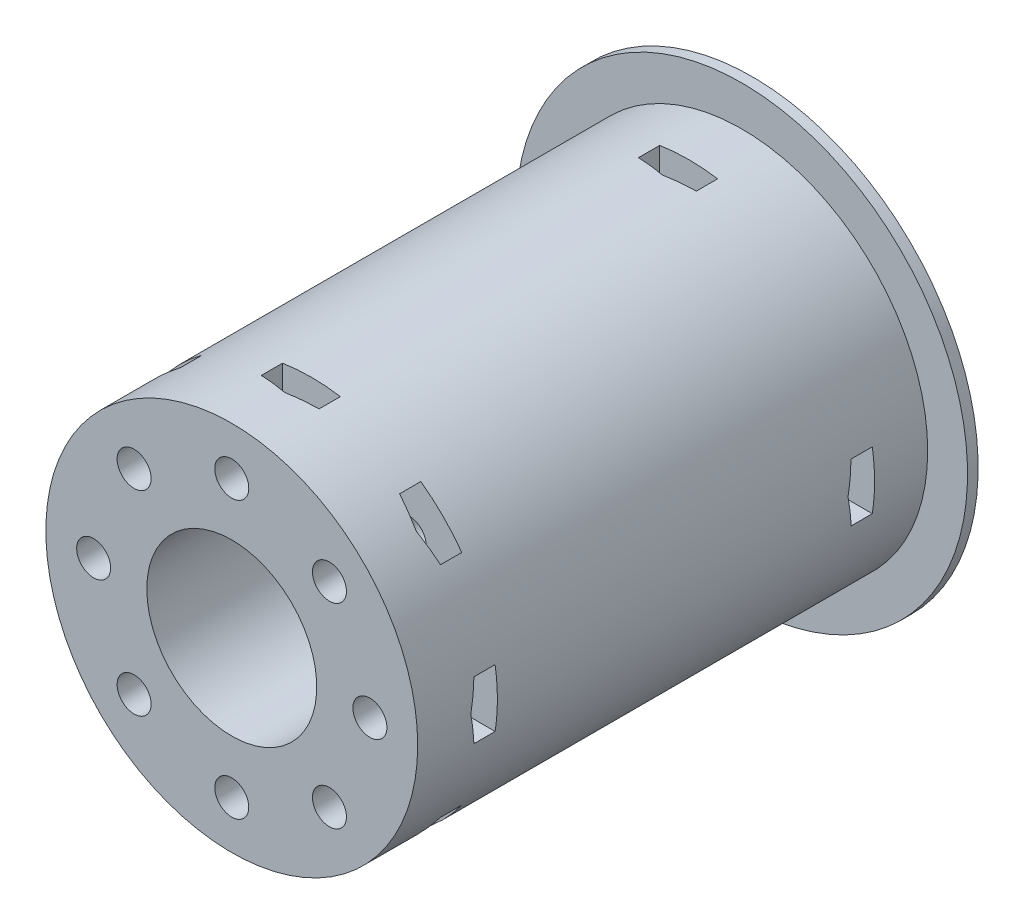
SolidWorks part; units mm, degrees
ref_plane "Front Plane" through (0, 0, 0) normal (1, 0, 0) x (0, 1, 0)
ref_plane "Top Plane" through (0, 0, 0) normal (0, 0, 1) x (0, 1, 0)
ref_plane "Right Plane" through (0, 0, 0) normal (0, 1, 0) x (-1, 0, 0)
sketch "Sketch1" plane through (0, 0, 0) normal (0, 0, 1) x (0, 1, 0)
  circle A0 centre (0, 0) radius 17.5
  dimension "D1" = 35
extrude "Boss-Extrude1" add sketch "Sketch1" along normal blind 24 and the other way blind 24
sketch "Sketch3" plane through (0, 0, -24) normal (0, 0, -1) x (1, 0, 0)
  circle A0 centre (0, 0) radius 21.25
  dimension "D1" = 42.5
extrude "Boss-Extrude2" add sketch "Sketch3" along normal blind 1
sketch "Sketch2" plane through (0, 0, 24) normal (0, 0, 1) x (1, 0, 0)
  line L0 (-2.725, 15.725) -> (-2.725, 17.2865)
  line L2 (-2.725, 15.725) -> (-2.725, 10.275)
  line L3 (-2.725, 10.275) -> (2.725, 10.275)
  line L4 (2.725, 15.725) -> (2.725, 10.275)
  line L5 (-2.725, 15.725) -> (2.725, 10.275) construction
  line L6 (-2.725, 10.275) -> (2.725, 15.725) construction
  line L7 (2.725, 15.725) -> (2.725, 17.2865)
  circle A0 centre (0, 0) radius 13 construction
  circle A1 centre (0, 13) radius 1.6
  circle A2 centre (0, 0) radius 17.5 construction
  arc A3 (-2.725, 17.2865) -> (2.725, 17.2865) centre (0, 0) cw
  dimension "D1" = 26
  dimension "D4" = 3.2
  dimension "D2" = 5.45
  dimension "D3" = 5.45
extrude "Cut-Extrude1" cut sketch "Sketch2" against normal through all contours A1
extrude "Cut-Extrude2" cut sketch "Sketch2<4>" against normal blind 2.5 from offset 5 offset against normal yes
sketch "Sketch2<4>" plane through (0, 0, 24) normal (0, 0, 1) x (1, 0, 0) same geometry as "Sketch2"
extrude "Cut-Extrude3" cut sketch "Sketch2<5>" along normal blind 2.5 from offset 43 offset against normal yes
sketch "Sketch2<5>" plane through (0, 0, 24) normal (0, 0, 1) x (1, 0, 0) same geometry as "Sketch2"
chamfer "Chamfer1" distance 2.725 distance2 0.5 2 edges at (-2.725, 13.7808, 19) (2.725, 13.7808, 19) first distance on face at (1.6, 13, 19)
chamfer "Chamfer2" distance 2.725 distance2 0.5 2 edges at (-2.725, 13.7808, -16.5) (2.725, 13.7808, -16.5) first distance on face at (0, 13.8341, -16.5)
pattern_circular "CirPattern1" count 8 over 360 about axis through (0, 0, -24) along (0, 0, 1) of "Cut-Extrude2", "Cut-Extrude1", "Chamfer1" reverse direction yes
pattern_circular "CirPattern3" count 4 over 360 about axis through (0, 0, -24) along (0, 0, 1) of "Cut-Extrude3", "Chamfer2"
sketch "Sketch4" plane through (0, 0, -25) normal (0, 0, -1) x (1, 0, 0)
  circle A0 centre (0, 0) radius 8
  dimension "D1" = 16
extrude "Cut-Extrude4" cut sketch "Sketch4" against normal through all both and the other way through all
sketch "Sketch5" plane through (0, 0, -25) normal (0, 0, -1) x (1, 0, 0)
  line L0 (-0.5, -10) -> (-0.5, -0.5)
  line L1 (-10, 0.5) -> (-0.5, 0.5)
  line L2 (-10, 0.5) -> (-10, -0.5)
  line L3 (-10, -0.5) -> (-0.5, -0.5)
  line L4 (10, 0.5) -> (10, -0.5)
  line L5 (-10, 0.5) -> (10, -0.5) construction
  line L6 (-10, -0.5) -> (10, 0.5) construction
  line L7 (-0.5, -10) -> (0.5, -10)
  line L8 (0.5, -10) -> (0.5, -0.5)
  line L9 (-0.5, 10) -> (0.5, 10)
  line L10 (-0.5, -10) -> (0.5, 10) construction
  line L11 (0.5, -10) -> (-0.5, 10) construction
  line L14 (-0.5, 0.5) -> (-0.5, 10)
  line L15 (0.5, 0.5) -> (0.5, 10)
  line L16 (0.5, 0.5) -> (10, 0.5)
  line L19 (0.5, -0.5) -> (10, -0.5)
  point P0 (0, 0)
  point P6 (0, 0)
  point P11 (0, 0)
  point P12 (23.112, -19.3365)
  dimension "D1" = 1
  dimension "D2" = 20
  dimension "D3" = 1
  dimension "D4" = 20
extrude "Cut-Extrude5" cut sketch "Sketch5" against normal blind 0.2
